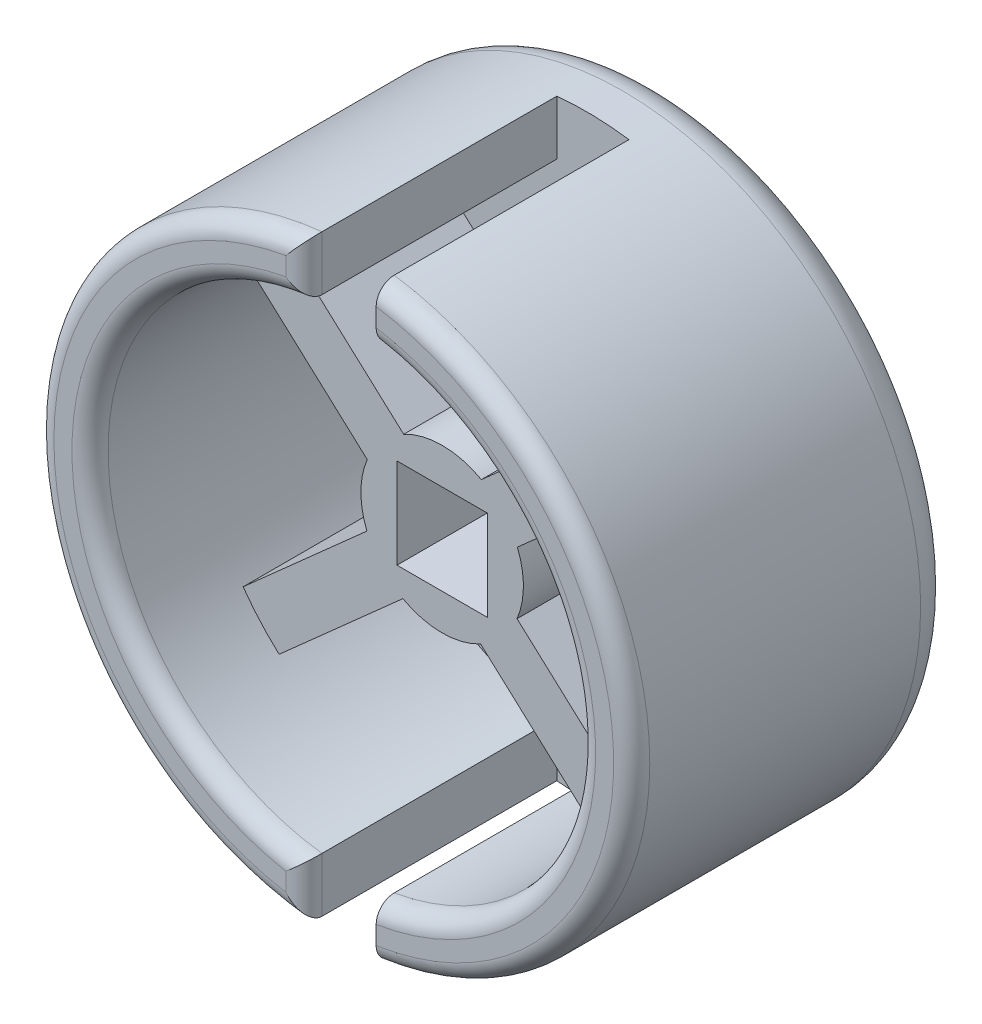
SolidWorks part; units mm, degrees
ref_plane "Спереди" through (0, 0, 0) normal (0, 0, 1) x (1, 0, 0)
ref_plane "Сверху" through (0, 0, 0) normal (0, 1, 0) x (1, 0, 0)
ref_plane "Справа" through (0, 0, 0) normal (1, 0, 0) x (0, 0, -1)
sketch "Эскиз1" plane through (0, 0, 0) normal (0, 0, 1) x (1, 0, 0)
  circle A0 centre (0, 0) radius 8.25
  dimension "D1" = 16.5
extrude "Вытянуть-Тонкостенный1" add sketch "Эскиз1" along normal blind 7 thin thin type one direction reverse wall 1.5
sketch "Эскиз2" plane through (0, 0, 0) normal (0, 0, -1) x (-1, 0, 0)
  circle A0 centre (0, 0) radius 8.25 construction
  circle A1 centre (0, 0) radius 8.25
extrude "Бобышка-Вытянуть1" add sketch "Эскиз2" along normal blind 2
sketch "Эскиз4" plane through (0, 0, 0) normal (0, 0, 1) x (1, 0, 0)
  line L2 (2.0741, -0.8722) -> (5.9686, -4.4135)
  line L4 (-5.9686, 4.4135) -> (-2.0741, 0.8722)
  line L5 (-5.9686, 4.4135) -> (-4.9595, 5.5233)
  line L6 (4.9595, -5.5233) -> (5.9686, -4.4135)
  line L7 (-4.9595, 5.5233) -> (-1.0649, 1.982)
  line L9 (1.0649, -1.982) -> (4.9595, -5.5233)
  line L10 (-5.9581, -4.2964) -> (-2.0834, -0.8496)
  line L11 (-5.9581, -4.2964) -> (-4.9611, -5.4171)
  line L12 (4.9611, 5.4171) -> (5.9581, 4.2964)
  line L13 (-4.9611, -5.4171) -> (-1.0865, -1.9703)
  line L22 (2.0834, 0.8496) -> (5.9581, 4.2964)
  line L23 (1.0865, 1.9703) -> (4.9611, 5.4171)
  arc A1 (1.0865, 1.9703) -> (-1.0649, 1.982) centre (0, 0) ccw
  arc A2 (-2.0741, 0.8722) -> (-2.0834, -0.8496) centre (0, 0) ccw
  arc A3 (-1.0865, -1.9703) -> (1.0649, -1.982) centre (0, 0) ccw
  arc A4 (2.0741, -0.8722) -> (2.0834, 0.8496) centre (0, 0) ccw
  dimension "D3" = 4.5
  dimension "D1" = 1.5
  dimension "D2" = 1.5
extrude "Бобышка-Вытянуть3" add sketch "Эскиз4" along normal blind 4
sketch "Эскиз3" plane through (0, 0, -2) normal (0, 0, -1) x (-1, 0, 0)
  line L1 (-1.25, 1.25) -> (1.25, 1.25)
  line L2 (-1.25, 1.25) -> (-1.25, -1.25)
  line L3 (-1.25, -1.25) -> (1.25, -1.25)
  line L4 (1.25, 1.25) -> (1.25, -1.25)
  line L5 (-1.25, 1.25) -> (1.25, -1.25) construction
  line L6 (-1.25, -1.25) -> (1.25, 1.25) construction
  point P0 (0, 0)
  dimension "D1" = 2.5
  dimension "D2" = 2.5
extrude "Вырез-Вытянуть1" cut sketch "Эскиз3" against normal through all
sketch "Эскиз6" plane through (0, 0, 7) normal (0, 0, 1) x (1, 0, 0)
  line L0 (-0.8263, 8.8467) -> (-0.8263, 5.5636)
  line L1 (1.1737, 5.5636) -> (1.1737, 8.8467)
  line L2 (1.1737, 8.8467) -> (-0.8263, 8.8467)
  line L3 (-0.8263, 5.5636) -> (1.1737, 5.5636)
  line L4 (-0.8263, -9.2874) -> (1.1737, -9.2874)
  line L5 (1.1737, -9.2874) -> (1.1737, -5.7399)
  line L6 (1.1737, -5.7399) -> (-0.8263, -5.7399)
  line L7 (-0.8263, -5.7399) -> (-0.8263, -9.2874)
  dimension "D1" = 2
  dimension "D2" = 2
extrude "Вырез-Вытянуть2" cut sketch "Эскиз6" against normal blind 7
fillet "Скругление1" radius 1 1 edges at (-8.25, 0, -2)
fillet "Скругление2" radius 0.5 6 edges at (-6.75, 0, 7) (-0.8263, -7.4539, 7) (-8.25, 0, 7) (-0.8263, 7.4539, 7) (8.25, 0, 7) (6.75, 0, 7)
